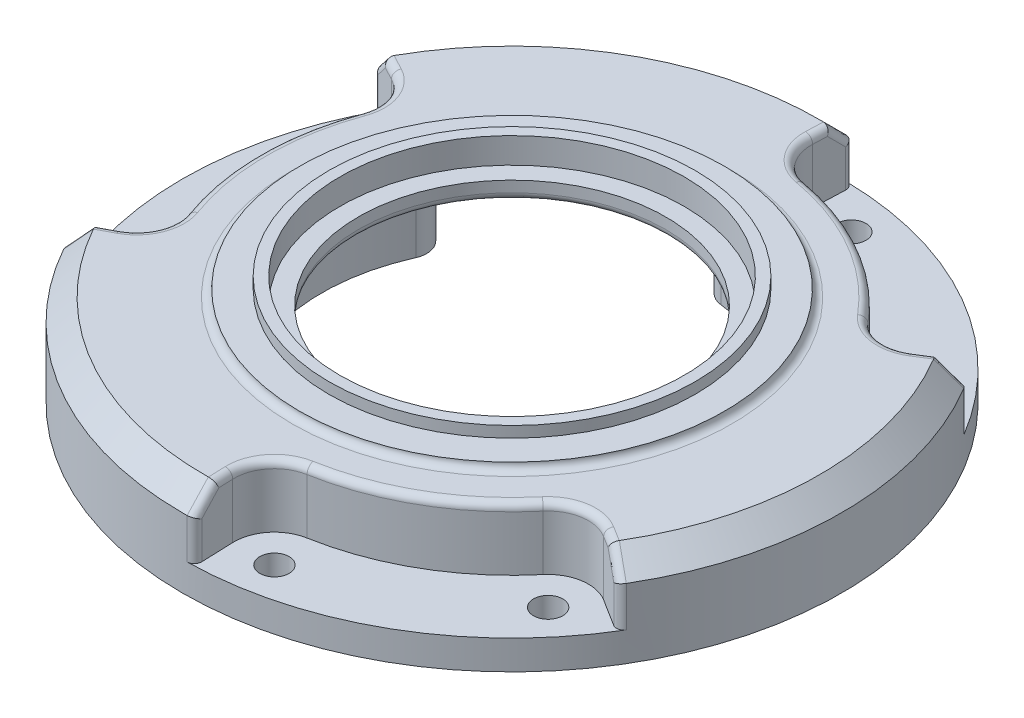
SolidWorks part; units mm, degrees
material "ABS"
ref_plane "Front Plane" through (0, 0, 0) normal (0, 0, 1) x (1, 0, 0)
ref_plane "Top Plane" through (0, 0, 0) normal (0, 1, 0) x (1, 0, 0)
ref_plane "Right Plane" through (0, 0, 0) normal (1, 0, 0) x (0, 0, -1)
sketch "Sketch1" plane through (0, 0, 0) normal (0, 0, 1) x (1, 0, 0)
  line L0 (-22.5, 7.5) -> (-22.5, -7.5) construction
  line L1 (22.5, -7.5) -> (22.5, 2)
  line L3 (22.5, -7.5) -> (17.5, -7.5)
  line L4 (2.5, 6) -> (6.5, 6)
  line L5 (1, 4) -> (-1.5, 4)
  line L6 (6.5, 6) -> (6.5, 5)
  line L7 (-1.5, 4) -> (-1.5, 1.5)
  line L9 (2.5, 7.5) -> (2.5, 6)
  line L10 (6.5, 5) -> (19.5, 5)
  line L11 (1, 7.5) -> (1, 4)
  line L12 (1, 7.5) -> (2.5, 7.5)
  line L13 (22.5, 2) -> (19.5, 5)
  line L14 (-1.5, 1.5) -> (-1.5, -7.5)
  line L15 (-1.5, -7.5) -> (17.5, -7.5)
revolve "Revolve1" add sketch "Sketch1" angle 360 about L0
sketch "Sketch2" plane through (0, 5, 0) normal (0, 1, 0) x (1, 0, 0)
  line L0 (-62.2683, 21.0591) -> (-57.5138, 18.5414)
  line L1 (-62.2683, -21.0591) -> (-57.5138, -18.5414)
  line L2 (-20.8536, -44.9699) -> (-21.0504, -39.5935)
  line L3 (15.6218, -23.9108) -> (11.0642, -21.0522)
  line L4 (15.6218, 23.9108) -> (11.0642, 21.0522)
  line L5 (-20.8536, 44.9699) -> (-21.0504, 39.5935)
  line L6 (-22.5, 45) -> (-22.5, -45) construction
  line L7 (-67.5, 0) -> (22.5, 0) construction
  arc A0 (-62.2683, 21.0591) -> (-62.2683, -21.0591) centre (-22.5, 0) ccw
  arc A1 (-54.9194, 11.7997) -> (-54.9194, -11.7997) centre (-22.5, 0) ccw
  arc A2 (-57.5138, -18.5414) -> (-54.9194, -11.7997) centre (-60.0877, -13.6808) ccw
  arc A3 (-54.9194, 11.7997) -> (-57.5138, 18.5414) centre (-60.0877, 13.6808) ccw
  arc A4 (-16.5091, -33.9759) -> (-21.0504, -39.5935) centre (-15.5541, -39.3923) ccw
  arc A5 (-16.5091, -33.9759) -> (3.9285, -22.1762) centre (-22.5, 0) ccw
  arc A6 (11.0642, -21.0522) -> (3.9285, -22.1762) centre (8.1418, -25.7115) ccw
  arc A7 (3.9285, 22.1762) -> (11.0642, 21.0522) centre (8.1418, 25.7115) ccw
  arc A8 (3.9285, 22.1762) -> (-16.5091, 33.9759) centre (-22.5, 0) ccw
  arc A9 (-21.0504, 39.5935) -> (-16.5091, 33.9759) centre (-15.5541, 39.3923) ccw
  circle A10 centre (-22.5, 0) radius 45 construction
  arc A11 (15.6218, 23.9108) -> (-20.8536, 44.9699) centre (-22.5, 0) ccw
  arc A12 (-20.8536, -44.9699) -> (15.6218, -23.9108) centre (-22.5, 0) ccw
extrude "Cut-Extrude1" cut sketch "Sketch2" against normal blind 8.5
sketch "Sketch3" plane through (0, 5, 0) normal (0, 1, 0) x (1, 0, 0)
  line L0 (-22.5, 45) -> (-22.5, -45) construction
  circle A0 centre (-60.0877, 13.6808) radius 2
  circle A1 centre (-60.0877, -13.6808) radius 2
  circle A3 centre (-15.5541, -39.3923) radius 2
  circle A4 centre (8.1418, -25.7115) radius 2
  circle A5 centre (8.1418, 25.7115) radius 2
  circle A6 centre (-15.5541, 39.3923) radius 2
  arc A7 (-20.8536, 44.9699) -> (-62.2683, 21.0591) centre (-22.5, 0) ccw construction
  arc A8 (-62.2683, -21.0591) -> (-20.8536, -44.9699) centre (-22.5, 0) ccw construction
extrude "Cut-Extrude2" cut sketch "Sketch3" against normal through all and the other way through all
sketch "Sketch5" plane through (0, -7.5, 0) normal (0, -1, 0) x (1, 0, 0)
  line L0 (-47.48, 14.4222) -> (-54.4374, 18.4391)
  line L1 (-47.48, -14.4222) -> (-54.4374, -18.4391)
  line L2 (-22.5, -28.8444) -> (-22.5, -36.8782)
  line L3 (2.48, -14.4222) -> (9.4374, -18.4391)
  line L4 (2.48, 14.4222) -> (9.4374, 18.4391)
  line L5 (-22.5, 28.8444) -> (-22.5, 36.8782)
  line L6 (-22.5, 45) -> (-22.5, -45) construction
  arc A0 (-55.4053, 22.7429) -> (-54.4374, 18.4391) centre (-52.9374, 21.0372) ccw
  arc A1 (-25.7432, 39.8683) -> (-55.4053, 22.7429) centre (-22.5, 0) ccw
  arc A2 (13.6486, -17.1254) -> (13.6486, 17.1254) centre (-22.5, 0) ccw
  arc A3 (-55.4053, -22.7429) -> (-25.7432, -39.8683) centre (-22.5, 0) ccw
  arc A4 (-54.4374, -18.4391) -> (-55.4053, -22.7429) centre (-52.9374, -21.0372) ccw
  arc A5 (-46.2407, 10.6009) -> (-46.2407, -10.6009) centre (-22.5, 0) ccw
  arc A6 (-46.2407, 10.6009) -> (-47.48, 14.4222) centre (-48.98, 11.8241) ccw
  arc A7 (-47.48, -14.4222) -> (-46.2407, -10.6009) centre (-48.98, -11.8241) ccw
  arc A8 (-25.7432, -39.8683) -> (-22.5, -36.8782) centre (-25.5, -36.8782) ccw
  arc A9 (9.4374, -18.4391) -> (13.6486, -17.1254) centre (10.9374, -15.841) ccw
  arc A10 (-19.8103, -25.8605) -> (-1.449, -15.2596) centre (-22.5, 0) ccw
  arc A11 (-19.8103, -25.8605) -> (-22.5, -28.8444) centre (-19.5, -28.8444) ccw
  arc A12 (2.48, -14.4222) -> (-1.449, -15.2596) centre (0.98, -17.0203) ccw
  arc A13 (13.6486, 17.1254) -> (9.4374, 18.4391) centre (10.9374, 15.841) ccw
  arc A14 (-22.5, 36.8782) -> (-25.7432, 39.8683) centre (-25.5, 36.8782) ccw
  arc A15 (-1.449, 15.2596) -> (-19.8103, 25.8605) centre (-22.5, 0) ccw
  arc A16 (-1.449, 15.2596) -> (2.48, 14.4222) centre (0.98, 17.0203) ccw
  arc A17 (-22.5, 28.8444) -> (-19.8103, 25.8605) centre (-19.5, 28.8444) ccw
  circle A18 centre (-22.5, 0) radius 45 construction
extrude "Cut-Extrude3" cut sketch "Sketch5" against normal blind 9
fillet "Zaokrąglenie1" radius 1 1 edges at (-22.5, 5, 29)
fillet "Zaokrąglenie2" radius 1 25 edges at (-22.5, 1.5, -21) (-50.9587, 1.5, 16.4306) (-55.8643, 1.5, 20.3789) (-42.5, 1.5, 34.641) (-23.4665, 1.5, 39.0838) (-22.5, 1.5, 32.8613) (-21.7283, 1.5, 26.8358) (-9.5, 1.5, 22.5167) (0.3547, 1.5, 14.0862) (5.9587, 1.5, 16.4306) (11.8308, 1.5, 18.7049) (17.5, 1.5, 0) (11.8308, 1.5, -18.7049) (5.9587, 1.5, -16.4306) (0.3547, 1.5, -14.0862) (-9.5, 1.5, -22.5167) (-21.7283, 1.5, -26.8358) (-22.5, 1.5, -32.8613) (-23.4665, 1.5, -39.0838) (-42.5, 1.5, -34.641) (-55.8643, 1.5, -20.3789) (-50.9587, 1.5, -16.4306) (-46.1263, 1.5, -12.7496) (-48.5, 1.5, 0) (-46.1263, 1.5, 12.7496)
fillet "Zaokrąglenie3" radius 1 27 edges at (-21.0069, 5, -40.7827) (-19.8313, 5, -35.9347) (-5.25, 5, -29.8779) (12.0723, 5, -21.6845) (-58.5654, 5, 19.0983) (-54.9547, 5, 15.6562) (-57, 5, 0) (-54.9547, 5, -15.6562) (12.0723, 5, 21.6845) (7.286, 5, 20.2785) (-5.25, 5, 29.8779) (-21.0069, 5, 40.7827) (-20.8536, -0.75, -44.9699) (-20.9084, 3.5, -43.4709) (7.286, 5, -20.2785) (14.3511, 3.5, -23.1138) (15.6218, -0.75, -23.9108) (-62.2683, -0.75, 21.0591) (-60.9427, 3.5, 20.3571) (-58.5654, 5, -19.0983) (-60.9427, 3.5, -20.3571) (-62.2683, -0.75, -21.0591) (15.6218, -0.75, 23.9108) (14.3511, 3.5, 23.1138) (-20.8536, -0.75, 44.9699) (-20.9084, 3.5, 43.4709) (-19.8313, 5, 35.9347)
